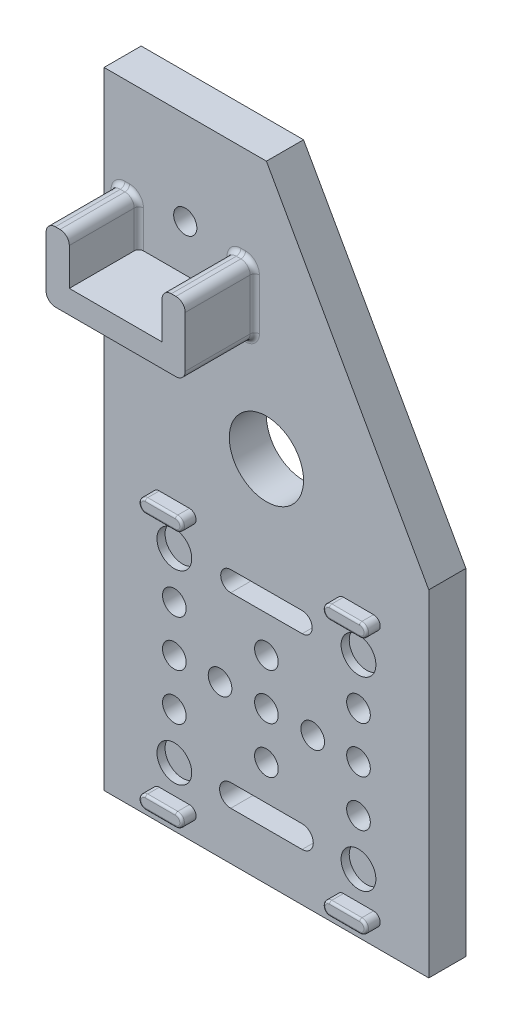
SolidWorks part; units mm, degrees
material "Plastique personnalisé"
ref_plane "Plan de face" through (0, 0, 0) normal (0, 0, 1) x (1, 0, 0)
ref_plane "Plan de dessus" through (0, 0, 0) normal (0, 1, 0) x (1, 0, 0)
ref_plane "Plan de droite" through (0, 0, 0) normal (1, 0, 0) x (0, 0, -1)
sketch "Esquisse1" plane through (0, 0, 0) normal (0, 0, 1) x (1, 0, 0)
  line L0 (0, 135) -> (35, 135) construction
  line L1 (0, 0) -> (70, 0)
  line L2 (0, 0) -> (0, 135)
  line L3 (0, 135) -> (35, 135)
  line L4 (70, 0) -> (70, 72.4723)
  line L5 (35, 135) -> (70, 72.4723) construction
  line L6 (35, 135) -> (70, 72.4723)
  line L7 (17.5, 135) -> (17.5, 115) construction
  circle A0 centre (17.5, 115) radius 2.5
  dimension "D1" = 70
  dimension "D2" = 135
  dimension "D3" = 20
extrude "Boss.-Extru.1" add sketch "Esquisse1" along normal blind 8
sketch "Esquisse3" plane through (0, 0, 0) normal (0, 0, -1) x (-1, 0, 0)
  line L0 (-35, 0) -> (-35, 38.3731) construction
  line L1 (0, 0) -> (-70, 0) construction
ref_axis "Axe1" through (35, -13.1714, 0) along (0, 1, 0)
sketch "Esquisse4" plane through (0, 0, 0) normal (0, 0, -1) x (-1, 0, 0)
  line L0 (-17.5, 115) -> (-17.5, 105) construction
  line L1 (-27.4969, 105) -> (-7.5031, 105)
  line L2 (-7.5031, 105) -> (-7.5031, 113)
  line L3 (-5.5031, 115) -> (-4.5044, 115)
  line L4 (-2.5044, 113) -> (-2.5044, 102.0044)
  line L5 (-4.5044, 100.0044) -> (-30.4956, 100.0044)
  line L6 (-32.4956, 113) -> (-32.4956, 102.0044)
  line L7 (-29.4969, 115) -> (-30.4956, 115)
  line L8 (-27.4969, 105) -> (-27.4969, 113)
  arc A0 (-29.4969, 115) -> (-27.4969, 113) centre (-29.4969, 113) cw
  arc A1 (-32.4956, 113) -> (-30.4956, 115) centre (-30.4956, 113) cw
  arc A2 (-32.4956, 102.0044) -> (-30.4956, 100.0044) centre (-30.4956, 102.0044) ccw
  arc A3 (-2.5044, 102.0044) -> (-4.5044, 100.0044) centre (-4.5044, 102.0044) cw
  arc A4 (-7.5031, 113) -> (-5.5031, 115) centre (-5.5031, 113) cw
  arc A5 (-4.5044, 115) -> (-2.5044, 113) centre (-4.5044, 113) cw
  point P9 (-17.5, 100.0044)
  point P14 (-27.4969, 115)
  point P17 (-32.4956, 115)
  point P20 (-32.4956, 100.0044)
  point P23 (-2.5044, 100.0044)
  point P26 (-7.5031, 115)
  point P29 (-2.5044, 115)
  dimension "D2" = 2
  dimension "D1" = 10
extrude "Boss.-Extru.3" add sketch "Esquisse4" along normal blind 15
fillet "Congé1" radius 1 13 edges at (27.4969, 109, 0) (28.0826, 114.4142, 0) (29.9962, 115, 0) (31.9098, 114.4142, 0) (32.4956, 107.5022, 0) (31.9098, 100.5902, 0) (17.5, 100.0044, 0) (7.5031, 109, 0) (6.9174, 114.4142, 0) (5.0038, 115, 0) (3.0902, 114.4142, 0) (2.5044, 107.5022, 0) (3.0902, 100.5902, 0)
sketch "Esquisse5" plane through (0, 0, 0) normal (0, 0, -1) x (-1, 0, 0)
  circle A0 centre (-54.85, 52.7483) radius 3.75
  circle A1 centre (-15.15, 52.7483) radius 3.75
  circle A2 centre (-54.85, 12.75) radius 3.75
  circle A3 centre (-15.15, 12.75) radius 3.75
extrude "Enlèv. mat.-Extru.1" cut sketch "Esquisse5" against normal blind 1.75
sketch "Esquisse6" plane through (0, 0, 0) normal (0, 0, -1) x (-1, 0, 0)
  circle A0 centre (-54.8469, 42.7525) radius 2.55
  circle A1 centre (-34.9977, 42.7525) radius 2.55
  circle A2 centre (-54.8469, 32.7887) radius 2.55
  circle A3 centre (-44.9846, 32.7887) radius 2.55
  circle A4 centre (-34.9977, 32.7887) radius 2.55
  circle A5 centre (-25.0004, 32.7887) radius 2.55
  circle A6 centre (-15.1504, 42.7525) radius 2.55
  circle A7 centre (-15.15, 32.7887) radius 2.55
  circle A8 centre (-15.15, 22.7468) radius 2.55
  circle A9 centre (-34.9977, 22.7468) radius 2.55
  circle A10 centre (-54.8469, 22.7468) radius 2.55
extrude "Enlèv. mat.-Extru.2" cut sketch "Esquisse6" against normal through all
sketch "Esquisse7" plane through (0, 0, 0) normal (0, 0, -1) x (-1, 0, 0)
  line L0 (-35, 55.0483) -> (-35, 50.4483) construction
  line L1 (-42.6949, 55.0483) -> (-27.3051, 55.0483) construction
  line L2 (-27.3051, 50.4483) -> (-42.6949, 50.4483) construction
  line L3 (-35, 52.7705) -> (-27.3051, 52.7483) construction
  line L4 (-42.6949, 52.7927) -> (-27.3051, 52.7483) construction
  line L5 (-42.6887, 54.9535) -> (-27.2988, 54.909)
  line L6 (-42.7012, 50.632) -> (-27.3113, 50.5876)
  line L7 (-35, 15.25) -> (-35, 10.25) construction
  line L8 (-42.6949, 15.25) -> (-27.3051, 15.25) construction
  line L9 (-27.3051, 10.25) -> (-42.6949, 10.25) construction
  line L10 (-35, 10.25) -> (-35, 12.75) construction
  line L11 (-35, 12.75) -> (-27.3051, 12.75) construction
  line L12 (-42.6949, 12.75) -> (-27.3051, 12.75) construction
  line L13 (-42.6949, 15.1528) -> (-27.3051, 15.1528)
  line L14 (-42.6949, 10.3472) -> (-27.3051, 10.3472)
  arc A0 (-42.6887, 54.9535) -> (-42.7012, 50.632) centre (-42.6949, 52.7927) ccw
  arc A1 (-27.3113, 50.5876) -> (-27.2988, 54.909) centre (-27.3051, 52.7483) ccw
  arc A2 (-42.6949, 15.1528) -> (-42.6949, 10.3472) centre (-42.6949, 12.75) ccw
  arc A3 (-27.3051, 10.3472) -> (-27.3051, 15.1528) centre (-27.3051, 12.75) ccw
  point P10 (-35, 52.7705)
  point P25 (-35, 12.75)
extrude "Enlèv. mat.-Extru.3" cut sketch "Esquisse7" against normal through all
sketch "Esquisse8" plane through (0, 0, 0) normal (0, 0, -1) x (-1, 0, 0)
  line L0 (-54.85, 61.9498) -> (-54.85, 58.9498) construction
  line L1 (-58.0962, 61.9498) -> (-51.6038, 61.9498) construction
  line L2 (-51.6038, 58.9498) -> (-58.0962, 58.9498) construction
  line L3 (-58.0962, 60.4498) -> (-51.6038, 60.4498) construction
  line L4 (-58.0962, 61.8873) -> (-51.6038, 61.8873)
  line L5 (-58.0962, 59.0123) -> (-51.6038, 59.0123)
  line L6 (-35, 65.5) -> (-35, 53.1144) construction
  line L7 (-35, 65.5) -> (-35, 0) construction
  line L8 (-11.9038, 60.4498) -> (-18.3962, 60.4498) construction
  line L9 (-11.9038, 61.8873) -> (-18.3962, 61.8873)
  line L10 (-11.9038, 59.0123) -> (-18.3962, 59.0123)
  line L11 (-54.8469, 32.7887) -> (-77.5585, 32.7887) construction
  line L12 (-58.0962, 5.1276) -> (-51.6038, 5.1276) construction
  line L13 (-58.0962, 3.6901) -> (-51.6038, 3.6901)
  line L14 (-58.0962, 6.5651) -> (-51.6038, 6.5651)
  line L15 (-11.9038, 5.1276) -> (-18.3962, 5.1276) construction
  line L16 (-11.9038, 3.6901) -> (-18.3962, 3.6901)
  line L17 (-11.9038, 6.5651) -> (-18.3962, 6.5651)
  arc A0 (-58.0962, 61.8873) -> (-58.0962, 59.0123) centre (-58.0962, 60.4498) ccw
  arc A1 (-51.6038, 59.0123) -> (-51.6038, 61.8873) centre (-51.6038, 60.4498) ccw
  arc A2 (-11.9038, 61.8873) -> (-11.9038, 59.0123) centre (-11.9038, 60.4498) cw
  arc A3 (-18.3962, 59.0123) -> (-18.3962, 61.8873) centre (-18.3962, 60.4498) cw
  arc A4 (-58.0962, 3.6901) -> (-58.0962, 6.5651) centre (-58.0962, 5.1276) cw
  arc A5 (-51.6038, 6.5651) -> (-51.6038, 3.6901) centre (-51.6038, 5.1276) cw
  arc A6 (-11.9038, 3.6901) -> (-11.9038, 6.5651) centre (-11.9038, 5.1276) ccw
  arc A7 (-18.3962, 6.5651) -> (-18.3962, 3.6901) centre (-18.3962, 5.1276) ccw
  point P8 (-54.85, 60.4498)
  point P21 (-15.15, 60.4498)
  point P31 (-54.85, 5.1276)
  point P38 (-15.15, 5.1276)
extrude "Boss.-Extru.4" add sketch "Esquisse8" along normal blind 3
fillet "Congé2" radius 0.5 16 edges at (19.8337, 5.1276, -3) (15.15, 6.5651, -3) (59.5337, 5.1276, -3) (54.85, 6.5651, -3) (19.8337, 60.4498, -3) (15.15, 61.8873, -3) (59.5337, 60.4498, -3) (54.85, 61.8873, -3) (15.15, 3.6901, -3) (10.4663, 5.1276, -3) (54.85, 3.6901, -3) (50.1663, 5.1276, -3) (15.15, 59.0123, -3) (10.4663, 60.4498, -3) (54.85, 59.0123, -3) (50.1663, 60.4498, -3)
sketch "Esquisse9" plane through (0, 0, 8) normal (0, 0, 1) x (1, 0, 0)
  line L0 (35, 0) -> (35, 163.9257) construction
  line L1 (35, -13.1714) -> (35, 38.3731) construction
ref_axis "Axe2dedans" through (35, 0, 8) along (0, 1, 0)
sketch "Esquisse10" plane through (0, 0, 0) normal (0, 0, -1) x (-1, 0, 0)
  circle A0 centre (-35, 79.4055) radius 12
  dimension "D1" = 24
extrude "Enlèv. mat.-Extru.4" cut sketch "Esquisse10" against normal through all
sketch "Esquisse11" plane through (0, 0, 0) normal (0, 0, -1) x (-1, 0, 0)
  circle A0 centre (-61, 71.8141) radius 2.5
  circle A1 centre (-9, 79.4043) radius 2.5
  circle A2 centre (-41, 105.4055) radius 2.5
extrude "Enlèv. mat.-Extru.5" cut sketch "Esquisse11" against normal through all
mirror "Symétrie1" about plane through (0, 0, 8) normal (0, 0, -1) of bodies 109
delete or keep bodies "Corps-Supprimer/Garder 1" type delete bodies bodies 109
sketch "Esquisse12" plane through (0, 0, 8) normal (0, 0, -1) x (-1, 0, 0)
  circle A0 centre (-35, 79.4055) radius 8
  circle A1 centre (-35, 79.4055) radius 12
  circle A2 centre (-41, 105.4055) radius 2.5
  circle A3 centre (-9, 79.4043) radius 2.5
  circle A4 centre (-61, 71.8141) radius 2.5
extrude "Boss.-Extru.5" add sketch "Esquisse12" against normal up to surface (8 mm away) up to face at (58.5, 71.8141, 16)
sketch "Esquisse13" plane through (0, 0, 8) normal (0, 0, -1) x (-1, 0, 0)
  circle A0 centre (-35, 79.4055) radius 8
  circle A1 centre (-35, 79.4055) radius 6.7329
